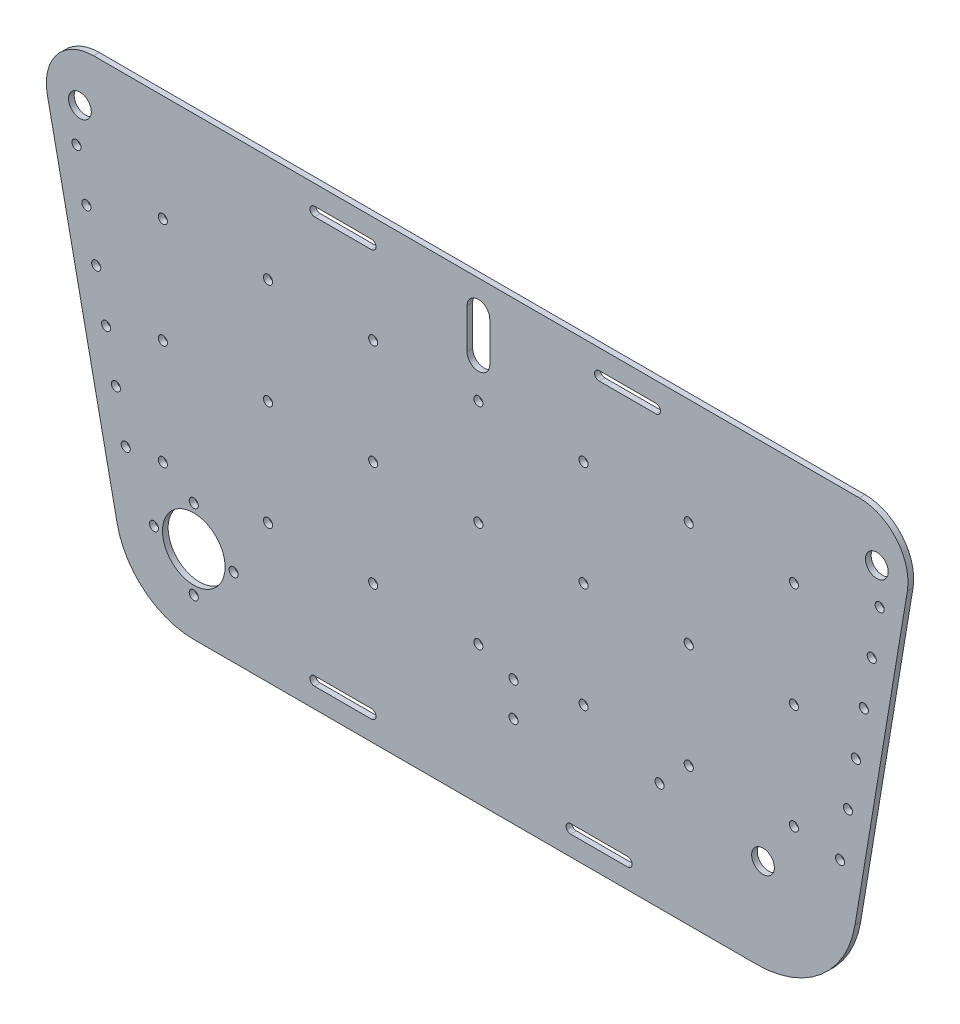
SolidWorks part; units mm, degrees
ref_plane "Front Plane" through (0, 0, 0) normal (0, 0, 1) x (1, 0, 0)
ref_plane "Top Plane" through (0, 0, 0) normal (0, 1, 0) x (1, 0, 0)
ref_plane "Right Plane" through (0, 0, 0) normal (1, 0, 0) x (0, 0, -1)
sketch "Sketch1" plane through (0, 0, 0) normal (0, 0, 1) x (1, 0, 0)
  line L1 (0, 0) -> (0, 115.062) construction
  line L2 (-140, 115.062) -> (140, 115.062) construction
  line L3 (-100, -37.4683) -> (100, -37.4683)
  line L4 (142.2945, 0.8576) -> (153.4347, 113.7361)
  line L5 (137.3964, 128.3085) -> (2.6036, 101.8154)
  line L6 (-2.6036, 101.8154) -> (-137.3964, 128.3085)
  line L7 (-153.3748, 113.2277) -> (-137.1523, -5.0634)
  line L8 (100, -34.9683) -> (-100, -34.9683) construction
  arc A12 (-137.1523, -5.0634) -> (-100, -37.4683) centre (-100, 0.0317) ccw
  arc A13 (100, -37.4683) -> (142.2945, 0.8576) centre (100, 5.0317) ccw
  arc A14 (153.4347, 113.7361) -> (137.3964, 128.3085) centre (140, 115.062) ccw
  arc A15 (2.6036, 101.8154) -> (-2.6036, 101.8154) centre (0, 115.062) cw
  arc A16 (-137.3964, 128.3085) -> (-153.3748, 113.2277) centre (-140, 115.062) ccw
  point P8 (0, 115.062)
  point P26 (0, -34.9683)
  circle B0 centre (-100, 0.0317) radius 35
  circle B1 centre (100, 5.0317) radius 40
  circle B2 centre (-140, 115.062) radius 11
  circle B3 centre (0, 115.062) radius 11
  circle B4 centre (140, 115.062) radius 11
  dimension "D1" = 200
  dimension "D3" = 280
  dimension "D7" = 279.5095
  dimension "D8" = 165.7768
sketch_block_instance "Block2-1"
sketch_block "Block2" parameters "D1"=52.784
sketch_block_instance "Block3-1"
sketch_block "Block3" parameters "D1"=49.6633
sketch_block_instance "Block4-1"
sketch_block "Block4"
sketch_block_instance "Block5-1"
sketch_block "Block5" parameters "D1"=22
sketch_block_instance "Block6-1"
sketch_block "Block6"
other "Belt1"
sketch "Sketch5" plane through (0, 0, 0) normal (0, 0, 1) x (1, 0, 0)
  line L12 (-100, -37.4683) -> (100, -37.4683) construction
  line L25 (110.1118, -2.4683) -> (77.5737, -2.4683)
  line L26 (65.3235, -2.4683) -> (34.5589, -2.4683)
  line L27 (134.4186, -22.4683) -> (143.6762, -22.4683)
  line L28 (143.4347, -2.4683) -> (134.6111, -2.4683)
  line L29 (143.4347, -2.4683) -> (143.4347, -22.4683)
  line L30 (16.6763, -22.4683) -> (134.2763, -22.4683)
  line L31 (15.513, -2.4683) -> (7.5179, -2.4683)
  line L32 (15.513, -22.4683) -> (7.5179, -22.4683)
  line L33 (7.5179, -2.4683) -> (7.5179, -22.4683)
  line L57 (14.6295, 0.5317) -> (66.6561, 0.5317)
  line L58 (66.6561, 0.5317) -> (66.6561, 7.0446)
  line L59 (66.6561, 14.0189) -> (66.6561, 20.5317)
  line L60 (66.6561, 20.5317) -> (14.6295, 20.5317)
  line L61 (10.0864, 20.5317) -> (8.6561, 20.5317)
  line L62 (8.6561, 20.5317) -> (8.6561, 19.2625)
  line L63 (8.6561, 13.801) -> (8.6561, 7.2625)
  line L64 (8.6561, 1.801) -> (8.6561, 0.5317)
  line L65 (8.6561, 0.5317) -> (10.0864, 0.5317)
  circle A0 centre (100, 5.0317) radius 11
  circle A2 centre (100, 5.0317) radius 7
  circle A29 centre (63.6561, 10.5317) radius 1.6
  circle A30 centre (12.3579, 16.5317) radius 1.6
  arc A36 (66.6561, 7.0446) -> (66.6561, 14.0189) centre (63.6561, 10.5317) ccw
  arc A37 (14.6295, 20.5317) -> (10.0864, 20.5317) centre (12.3579, 16.5317) ccw
  arc A38 (8.6561, 19.2625) -> (8.6561, 13.801) centre (12.3579, 16.5317) ccw
  arc A39 (8.6561, 7.2625) -> (8.6561, 1.801) centre (12.3579, 4.5317) ccw
  arc A40 (10.0864, 0.5317) -> (14.6295, 0.5317) centre (12.3579, 4.5317) ccw
  circle A41 centre (12.3579, 4.5317) radius 1.6
  dimension "D1" = 3.2
  dimension "D2" = 4.6
  dimension "D23" = 22
  dimension "D24" = 14
  dimension "D3" = 1.1383
  dimension "D4" = 2.5685
  dimension "D5" = 4.8401
  dimension "D6" = 136.1584
  dimension "D7" = 7.9951
  dimension "D8" = 9.1584
  dimension "D9" = 27.0411
  dimension "D10" = 56.1383
  dimension "D11" = 57.8057
  dimension "D12" = 59.1383
  dimension "D13" = 70.0559
  dimension "D14" = 102.594
  dimension "D15" = 126.7584
  dimension "D16" = 126.9007
  dimension "D17" = 127.0932
  dimension "D18" = 135.9169
  dimension "D19" = 20
  dimension "D20" = 23
  dimension "D21" = 29.5129
  dimension "D22" = 15
  dimension "D25" = 10
sketch "Sketch3" plane through (0, 0, 0) normal (0, 0, 1) x (1, 0, 0)
  line L0 (-100, -27.4683) -> (97.7714, -27.4683)
  line L1 (-100, -37.4683) -> (100, -37.4683) construction
  line L2 (-126.9257, -5.5588) -> (-151.4564, 112.5875)
  line L3 (132.3429, 1.8398) -> (150.7181, 112.5875)
  line L4 (-137.1523, -5.0634) -> (-126.9257, -5.5588) construction
  line L6 (142.2945, 0.8576) -> (132.3429, 1.8398) construction
  line L7 (142.2945, 0.8576) -> (153.4347, 113.7361) construction
  line L8 (-135.2278, 132.5317) -> (133.8103, 132.5317)
  line L9 (-4, 121.9902) -> (-4, 108.1338)
  line L10 (4, 121.9902) -> (4, 108.1338)
  circle A0 centre (-140, 115.062) radius 4
  circle A1 centre (0, 115.062) radius 4
  circle A2 centre (140, 115.062) radius 4
  circle A3 centre (100, 5.0317) radius 4
  circle A4 centre (-100, 0.0317) radius 11
  circle A6 centre (140, 115.062) radius 11 construction
  arc A7 (-100, -27.4683) -> (-126.9257, -5.5588) centre (-100, 0.0317) cw
  arc A8 (97.7714, -27.4683) -> (132.3429, 1.8398) centre (97.7714, 7.5758) ccw
  arc A10 (-151.4564, 112.5875) -> (-135.2278, 132.5317) centre (-135.2278, 115.9571) cw
  arc A11 (150.7181, 112.5875) -> (133.8103, 132.5317) centre (133.8103, 115.3929) ccw
  circle A13 centre (63.6561, 10.5317) radius 1.6 construction
  circle A14 centre (12.3579, 4.5317) radius 1.6 construction
  circle A15 centre (12.3579, 16.5317) radius 1.6 construction
  circle A16 centre (63.6561, 10.5317) radius 1.6
  circle A17 centre (12.3579, 4.5317) radius 1.6
  circle A18 centre (12.3579, 16.5317) radius 1.6
  circle A19 centre (-100, 0.0317) radius 14 construction
  circle A20 centre (-100, 14.0317) radius 1.6
  circle A21 centre (-86, 0.0317) radius 1.6
  circle A22 centre (-100, -13.9683) radius 1.6
  circle A23 centre (-114, 0.0317) radius 1.6
  circle A24 centre (0, 115.062) radius 8 construction
  arc A25 (-4, 121.9902) -> (4, 121.9902) centre (0, 121.9902) cw
  arc A26 (-4, 108.1338) -> (4, 108.1338) centre (0, 108.1338) ccw
  dimension "D1" = 8
  dimension "D5" = 22
  dimension "D6" = 28
  dimension "D7" = 3.2
  dimension "D2" = 10
  dimension "D3" = 10
  dimension "D4" = 160
  dimension "D9" = 8
  dimension "D8" = 4
extrude "Boss-Extrude1" add sketch "Sketch3" along normal blind 2 contours A10 L2 A7 L0 A8 L3 A11 L8 A26 L9 A25 L10 A23 A22 A21 A20 A18 A17 A16 A4 A3 A2 A0 region at (1.4431, 55.8088, 0)
sketch "Sketch6" plane through (0, 0, 0) normal (0, 0, 1) x (1, 0, 0)
  line L0 (-57.58, -17.2983) -> (-37.58, -17.2983)
  line L1 (-57.58, -20.4983) -> (-37.58, -20.4983)
  line L2 (32.42, -17.2983) -> (52.42, -17.2983)
  line L3 (32.42, -20.4983) -> (52.42, -20.4983)
  line L4 (-100, -27.4683) -> (97.7714, -27.4683) construction
  line L5 (32.42, -18.8983) -> (-37.58, -18.8983) construction
  line L6 (-25.08, -27.4683) -> (-25.08, 132.5317) construction
  line L7 (-135.2278, 132.5317) -> (133.8103, 132.5317) construction
  line L8 (-25.08, 52.5317) -> (-5.468, 52.5317) construction
  line L9 (-57.58, 125.5617) -> (-37.58, 125.5617)
  line L10 (-57.58, 122.3617) -> (-37.58, 122.3617)
  line L11 (42.42, 125.5617) -> (62.42, 125.5617)
  line L12 (42.42, 122.3617) -> (62.42, 122.3617)
  arc A0 (-57.58, -17.2983) -> (-57.58, -20.4983) centre (-57.58, -18.8983) ccw
  arc A1 (-37.58, -17.2983) -> (-37.58, -20.4983) centre (-37.58, -18.8983) cw
  arc A2 (52.42, -17.2983) -> (52.42, -20.4983) centre (52.42, -18.8983) cw
  arc A3 (32.42, -17.2983) -> (32.42, -20.4983) centre (32.42, -18.8983) ccw
  arc A4 (-37.58, 122.3617) -> (-37.58, 125.5617) centre (-37.58, 123.9617) ccw
  arc A5 (-57.58, 122.3617) -> (-57.58, 125.5617) centre (-57.58, 123.9617) cw
  arc A6 (42.42, 122.3617) -> (42.42, 125.5617) centre (42.42, 123.9617) cw
  arc A7 (62.42, 122.3617) -> (62.42, 125.5617) centre (62.42, 123.9617) ccw
  point P6 (-47.58, -17.2983)
  dimension "D1" = 3.2
  dimension "D2" = 52.42
  dimension "D3" = 20
  dimension "D5" = 8.57
  dimension "D6" = 2
  dimension "D7" = 70
  dimension "D4" = 2
extrude "Cut-Extrude3" cut sketch "Sketch6" along normal through all
ref_plane "Plane1" through (0, 52.5317, 0) normal (0, -1, 0) x (-1, 0, 0)
sketch "Sketch7" plane through (0, 0, 2) normal (0, 0, 1) x (1, 0, 0)
  line L0 (0, 95.0743) -> (0, 104.1338) construction
  line L1 (-88.8055, 84.3587) -> (-73.8055, 84.3587) construction
  line L2 (-88.8055, 84.3587) -> (-88.8055, 69.3587) construction
  line L3 (-88.8055, 69.3587) -> (-73.8055, 69.3587) construction
  line L4 (-73.8055, 84.3587) -> (-73.8055, 69.3587) construction
  line L5 (-88.8055, 84.3587) -> (-73.8055, 69.3587) construction
  line L6 (-88.8055, 69.3587) -> (-73.8055, 84.3587) construction
  line L7 (-141.1844, 102.4668) -> (-121.897, 9.5732) construction
  line L8 (-126.9257, -5.5588) -> (-151.4564, 112.5875) construction
  line L9 (-1.1, 52.5317) -> (1.1, 52.5317) construction
  line L10 (140.9921, 102.8439) -> (122.5363, -8.3891) construction
  line L12 (132.3429, 1.8398) -> (150.7181, 112.5875) construction
  circle A0 centre (-110.8622, 95.0743) radius 1.6
  circle A1 centre (-73.9081, 95.0743) radius 1.6
  circle A2 centre (-36.9541, 95.0743) radius 1.6
  circle A3 centre (0, 95.0743) radius 1.6
  circle A4 centre (36.9541, 95.0743) radius 1.6
  circle A5 centre (73.9081, 95.0743) radius 1.6
  circle A6 centre (110.8622, 95.0743) radius 1.6
  circle A7 centre (-73.9081, 58.0743) radius 1.6
  circle A8 centre (-36.9541, 58.0743) radius 1.6
  circle A9 centre (0, 58.0743) radius 1.6
  circle A10 centre (36.9541, 58.0743) radius 1.6
  circle A11 centre (73.9081, 58.0743) radius 1.6
  circle A12 centre (110.8622, 58.0743) radius 1.6
  circle A13 centre (-73.9081, 21.0743) radius 1.6
  circle A14 centre (-36.9541, 21.0743) radius 1.6
  circle A15 centre (0, 21.0743) radius 1.6
  circle A16 centre (36.9541, 21.0743) radius 1.6
  circle A17 centre (73.9081, 21.0743) radius 1.6
  circle A18 centre (110.8622, 21.0743) radius 1.6
  circle A19 centre (-110.8622, 58.0743) radius 1.6
  circle A20 centre (-110.8622, 21.0743) radius 1.6
  arc A21 (-4, 108.1338) -> (4, 108.1338) centre (0, 108.1338) ccw construction
  circle A22 centre (-141.1844, 102.4668) radius 1.6
  circle A23 centre (-137.7284, 85.8218) radius 1.6
  circle A24 centre (-134.2724, 69.1767) radius 1.6
  circle A25 centre (-130.8164, 52.5317) radius 1.6
  circle A26 centre (-127.3604, 35.8867) radius 1.6
  circle A27 centre (-123.9044, 19.2417) radius 1.6
  circle A28 centre (140.9921, 102.8439) radius 1.6
  circle A29 centre (138.2095, 86.0732) radius 1.6
  circle A30 centre (135.4269, 69.3025) radius 1.6
  circle A31 centre (132.6443, 52.5317) radius 1.6
  circle A32 centre (129.8617, 35.761) radius 1.6
  circle A33 centre (127.0791, 18.9903) radius 1.6
  point P0 (-81.3055, 76.8587)
  dimension "D1" = 3.2
  dimension "D4" = 6
  dimension "D6" = 8
  dimension "D2" = 7
  dimension "D5" = 8
  dimension "D3" = 3
  dimension "D7" = 6
extrude "Cut-Extrude4" cut sketch "Sketch7" against normal through all
